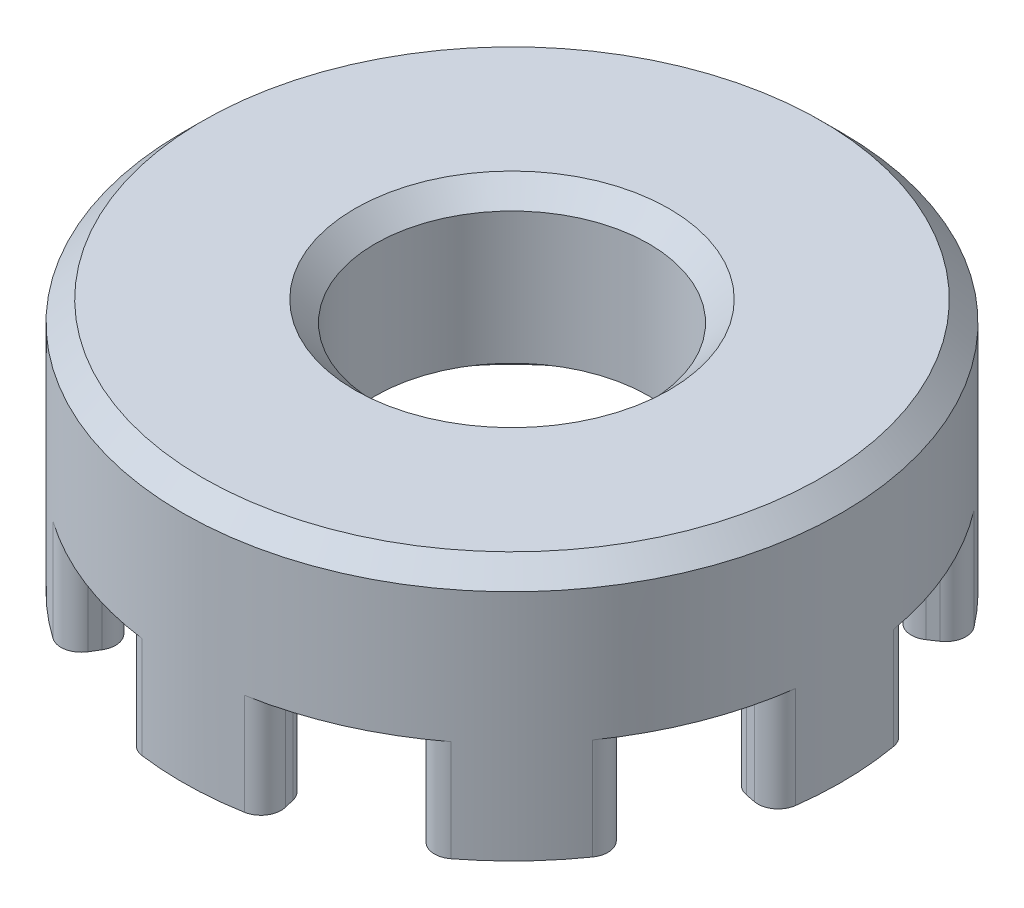
SolidWorks part; units mm, degrees
ref_plane "Front Plane" through (0, 0, 0) normal (0, 0, 1) x (1, 0, 0)
ref_plane "Top Plane" through (0, 0, 0) normal (0, 1, 0) x (1, 0, 0)
ref_plane "Right Plane" through (0, 0, 0) normal (1, 0, 0) x (0, 0, -1)
sketch "Sketch1" plane through (0, 0, 0) normal (0, 1, 0) x (1, 0, 0)
  circle A0 centre (0, 0) radius 2.7
  circle A1 centre (0, 0) radius 6.5
  circle A2 centre (0, 0) radius 5.5
  dimension "D1" = 5.4
  dimension "D2" = 13
  dimension "D3" = 11
extrude "Boss-Extrude1" add sketch "Sketch1" along normal blind 3 contours A2 A0 | A1 A2 region at (-6.3162, 0, 0) region at (-5.3444, 0, 0)
extrude "Boss-Extrude2" add sketch "Sketch1<3>" against normal blind 2 contours A1 A2 region at (-6.3162, 0, 0)
sketch "Sketch1<3>" plane through (0, 0, 0) normal (0, 1, 0) x (1, 0, 0) same geometry as "Sketch1"
sketch "Sketch2" plane through (0, -2, 0) normal (0, -1, 0) x (-1, 0, 0)
  line L0 (0, 0) -> (3.375, -5.5551)
  line L1 (0, 0) -> (1.2715, -6.3744)
  line L2 (3.375, -5.5551) -> (3.375, -6.3744)
  line L3 (3.375, -6.3744) -> (1.2715, -6.3744)
  circle A0 centre (0, 0) radius 6.5 construction
  dimension "D1" = 20
extrude "Cut-Extrude1" cut sketch "Sketch2" against normal blind 2
pattern_circular "CirPattern1" count 8 over 360 about axis through (0, 3, 0) along (0, -1, 0) of "Cut-Extrude1" reverse direction yes
fillet "Fillet2" radius 0.4 32 edges at (6.3145, -1, -1.5416) (5.4065, -1, -3.6083) (3.375, -1, -5.5551) (1.2715, -1, -6.3744) (-1.5416, -1, -6.3145) (-3.6083, -1, -5.4065) (-5.5551, -1, -3.375) (-6.3744, -1, -1.2715) (-6.3145, -1, 1.5416) (-5.4065, -1, 3.6083) (-3.375, -1, 5.5551) (-1.2715, -1, 6.3744) (1.5416, -1, 6.3145) (3.6083, -1, 5.4065) (5.5551, -1, 3.375) (6.3744, -1, 1.2715) (2.8558, -1, -4.7005) (4.5747, -1, -3.0532) (5.3431, -1, -1.3044) (5.3937, -1, 1.0759) (4.7005, -1, 2.8558) (3.0532, -1, 4.5747) (1.3044, -1, 5.3431) (-1.0759, -1, 5.3937) (-2.8558, -1, 4.7005) (-4.5747, -1, 3.0532) (-5.3431, -1, 1.3044) (-5.3937, -1, -1.0759) (-4.7005, -1, -2.8558) (-3.0532, -1, -4.5747) (1.0759, -1, -5.3937) (-1.3044, -1, -5.3431)
chamfer "Chamfer1" distance 0.4 angle 45 2 edges at (0, 3, 6.5) (0, 3, 2.7)
